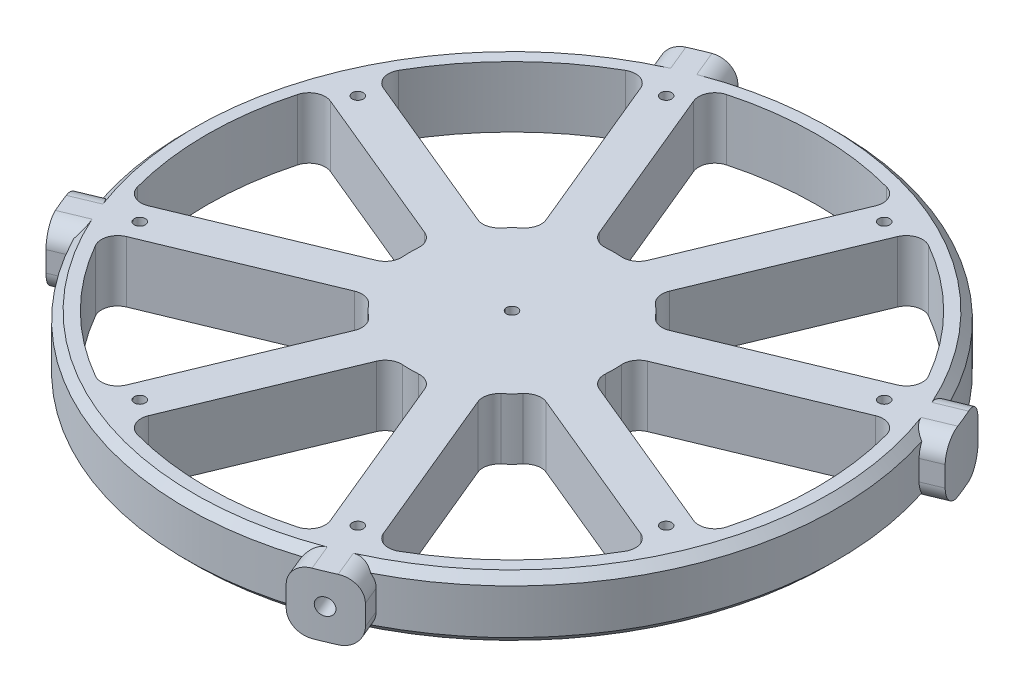
SolidWorks part; units mm, degrees
ref_plane "Front Plane" through (0, 0, 0) normal (0, 0, 1) x (1, 0, 0)
ref_plane "Top Plane" through (0, 0, 0) normal (0, 1, 0) x (1, 0, 0)
ref_plane "Right Plane" through (0, 0, 0) normal (1, 0, 0) x (0, 0, -1)
sketch "Sketch2" plane through (0, 0, 0) normal (1, 0, 0) x (0, 0, -1)
  line L0 (0, 0) -> (-79.9998, 0)
  line L1 (-79.9998, 0) -> (-79.9998, 15)
  line L2 (-79.9998, 15) -> (0, 15)
  line L5 (0, 15) -> (0, 0)
  dimension "D1" = 79.9998
  dimension "D2" = 15
ref_axis "Axis1" through (0, -1.0952, 0) along (0, 1, 0)
revolve "Revolve1" add sketch "Sketch2" angle 360 about axis through (0, -1.0952, 0) along (0, 1, 0)
hole_wizard "#6-32 Tapped Hole2" positions "Sketch6" profile "Sketch7" tap size "#6-32" standard "ANSI Inch" end condition through all
sketch "Sketch6" plane through (0, 15, 0) normal (0, 1, 0) x (1, 0, 0)
  line L0 (0, 0) -> (-53.438, 129.0108) construction
  line L2 (0, 0) -> (0, 109.0908) construction
  point P0 (-26.7878, 64.6716)
  dimension "D1" = 22.5
  dimension "D2" = 70
sketch "Sketch7" plane through (-26.7878, 15, -64.6716) normal (1, 0, 0) x (0, 0, 1)
  line L0 (0, 0) -> (0, 15)
  line L1 (0, 15) -> (1.3525, 15)
  line L2 (1.3525, 15) -> (1.3525, 0)
  line L5 (1.3525, 0) -> (0, 0)
  line L11 (0, -6.35) -> (0, 107.95) construction
  dimension "Thread Major Dia." = 2.7051
  dimension "Thru Tap Drill Depth" = 15
pattern_circular "CirPattern3" count 8 over 360 about axis through (0, -1.0952, 0) along (0, 1, 0) of "#6-32 Tapped Hole2"
sketch "Sketch8" plane through (0, 15, 0) normal (0, 1, 0) x (1, 0, 0)
  line L4 (0, 0) -> (0, 93.9995) construction
  line L5 (0, 0) -> (113.8372, 0) construction
  line L6 (-4.7544, 24.5438) -> (-24.0179, 71.0501)
  line L7 (4.7544, 24.5438) -> (24.0179, 71.0501)
  line L8 (0, 0) -> (-26.7878, 64.6716) construction
  arc A0 (-4.7544, 24.5438) -> (4.7544, 24.5438) centre (0, 0) cw
  arc A1 (-24.0179, 71.0501) -> (24.0179, 71.0501) centre (0, 0) cw
  circle A2 centre (0, 0) radius 79.9998 construction
  dimension "D1" = 25
  dimension "D2" = 5
  dimension "D3" = 5
extrude "Cut-Extrude1" cut sketch "Sketch8" against normal through all
fillet "Fillet1" radius 4 4 edges at (4.7544, 7.5, -24.5438) (24.0179, 7.5, -71.0501) (-4.7544, 7.5, -24.5438) (-24.0179, 7.5, -71.0501)
pattern_circular "CirPattern4" count 8 over 360 about axis through (0, -1.0952, 0) along (0, 1, 0) of "Cut-Extrude1", "Fillet1"
hole_wizard "#6-32 Tapped Hole1" positions "Sketch9" profile "Sketch11" tap size "#6-32" standard "ANSI Inch" end condition through all
sketch "Sketch9" plane through (0, 0, 0) normal (0, -1, 0) x (-1, 0, 0)
  point P0 (0, 0)
sketch "Sketch11" plane through (0, 0, 0) normal (1, 0, 0) x (0, 0, -1)
  line L0 (0, 0) -> (0, 15)
  line L1 (0, 15) -> (1.3525, 15)
  line L2 (1.3525, 15) -> (1.3525, 0)
  line L5 (1.3525, 0) -> (0, 0)
  line L11 (0, -6.35) -> (0, 107.95) construction
  dimension "Thru Tap Drill Dia." = 2.7051
  dimension "Thru Tap Drill Depth" = 15
cosmetic thread "Hole Thread1" parameters "D2"=3.5052
sketch "Sketch12" plane through (0, 15, 0) normal (0, 1, 0) x (1, 0, 0)
  line L0 (0, 0) -> (-26.7878, 64.6716) construction
  line L1 (-23.5987, 76.44) -> (-25.4738, 80.967)
  line L2 (-39.2396, 75.265) -> (-37.3645, 70.738)
  circle A0 centre (0, 0) radius 79.9998 construction
  arc A1 (-25.4738, 80.967) -> (-39.2396, 75.265) centre (0, 0) ccw
  circle A2 centre (0, 0) radius 79.9998 construction
  arc A3 (-37.3645, 70.738) -> (-23.5987, 76.44) centre (0, 0) cw
  dimension "D1" = 14.9
  dimension "D2" = 4.9
extrude "Boss-Extrude1" add sketch "Sketch12" against normal blind 15
fillet "Fillet2" radius 5 4 edges at (-24.5362, 15, -78.7035) (-38.302, 15, -73.0015) (-24.5362, 0, -78.7035) (-38.302, 0, -73.0015)
pattern_circular "CirPattern5" count 4 over 360 about axis through (0, -1.0952, 0) along (0, 1, 0) of "Fillet2", "Boss-Extrude1"
chamfer "Chamfer1" distance 2 angle 45 8 edges at (73.9102, 0, 30.6146) (-30.6146, 0, 73.9102) (-73.9102, 0, -30.6146) (-73.9102, 15, -30.6146) (-30.6146, 15, 73.9102) (73.9102, 15, 30.6146) (30.6146, 0, -73.9102) (30.6146, 15, -73.9102)
ref_plane "Plane1" through (0, 0, 0) normal (0.3827, 0, 0.9239) x (0, 1, 0)
hole_wizard "#20 (0.161) Diameter Hole1" positions "Sketch16" profile "Sketch15" hole size "#20" standard "ANSI Inch" end condition through all
sketch "Sketch16" plane through (0, 0, 0) normal (0.3827, 0, 0.9239) x (0, 1, 0)
  point P0 (7.5, 0)
  dimension "D1" = 7.5
sketch "Sketch15" plane through (0, 7.5, 0) normal (0, 1, 0) x (-0.9239, 0, 0.3827)
  line L0 (0, 0) -> (0, 106.1589)
  line L1 (0, 106.1589) -> (2.0447, 106.1589)
  line L2 (2.0447, 106.1589) -> (2.0447, 0)
  line L5 (2.0447, 0) -> (0, 0)
  line L11 (0, -6.35) -> (0, 107.95) construction
  dimension "Thru Hole Dia." = 4.0894
  dimension "Thru Hole Depth" = 106.1589
equation "\"TubeDiameter\" = 6.6929in"
equation "\"D1@Sketch2\"=(\"TubeDiameter\"/2)-5mm"
